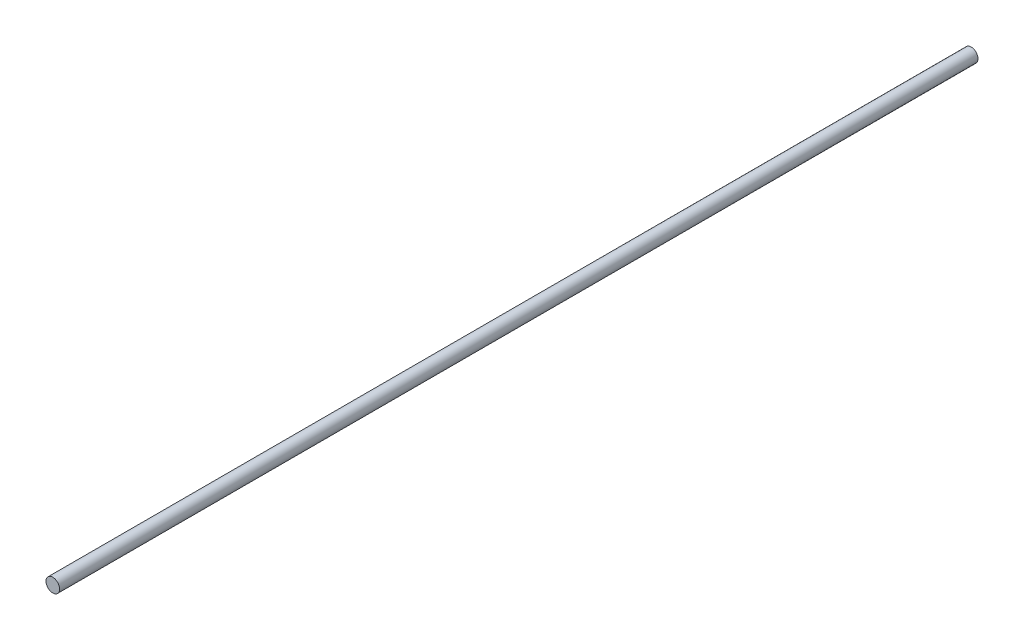
SolidWorks part; units mm, degrees
ref_plane "Front Plane" through (0, 0, 0) normal (0, 0, 1) x (1, 0, 0)
ref_plane "Top Plane" through (0, 0, 0) normal (0, 1, 0) x (1, 0, 0)
ref_plane "Right Plane" through (0, 0, 0) normal (1, 0, 0) x (0, 0, -1)
sketch "Sketch1" plane through (0, 0, 0) normal (0, 0, 1) x (1, 0, 0)
  circle A0 centre (0, 0) radius 4
  dimension "D1" = 8
extrude "Boss-Extrude1" add sketch "Sketch1" against normal blind 540
ref_plane "Plane2" through (0, 0, 1) normal (0, 0, 1) x (1, 0, 0)
sketch "Sketch2" plane through (0, 0, 1) normal (0, 0, 1) x (1, 0, 0)
  circle A1 centre (0, 0) radius 4.05
  dimension "D1" = 8.1
curve "Helix/Spiral1" pitch 8 height 540 turns 67.5
sketch "Sketch3" plane through (0, 0, 1) normal (0, 0, 1) x (1, 0, 0)
  circle A0 centre (0, 0) radius 4
  circle A1 centre (0, 0) radius 4
  circle A2 centre (0, 0) radius 4
  dimension "D1" = 0
sketch "Sketch4" plane through (0, 0, 1) normal (0, 0, 1) x (1, 0, 0)
  circle A0 centre (0, 0) radius 4 construction
  circle A1 centre (0, 0) radius 4
curve "Helix/Spiral2" pitch 8 height 540 turns 67.5
sketch "Sketch5" plane through (0, 0, 1) normal (0, 0, 1) x (1, 0, 0)
  circle A0 centre (0, 0) radius 4 construction
  circle A1 centre (0, 0) radius 4
curve "Helix/Spiral3" pitch 8 height 540 turns 67.5
sketch "Sketch6" plane through (0, 0, 1) normal (0, 0, 1) x (1, 0, 0)
  circle A0 centre (0, 0) radius 4 construction
  circle A1 centre (0, 0) radius 4
curve "Helix/Spiral4" pitch 8 height 540 turns 67.5
sketch "Sketch10" plane through (0, 0, 0) normal (0, 1, 0) x (1, 0, 0)
  line L0 (4.05, -1.67) -> (4.05, -0.33)
  line L1 (2.9, -1.3619) -> (2.9, -0.6519)
  line L2 (2.9, -1.3619) -> (4.05, -1.67)
  line L7 (2.9, -0.6519) -> (4.05, -0.33)
  point P4 (4.05, -1)
  dimension "D6" = 0.71
  dimension "D9" = 1.34
  dimension "D10" = 75
  dimension "D11" = 1.15
sweep "Cut-Sweep3" [suppressed] cut profiles "Sketch10" path "Helix/Spiral1"
sketch "Sketch11" plane through (0, 0, 0) normal (1, 0, 0) x (0, 0, -1)
  line L0 (2.33, -4) -> (3.67, -4)
  line L5 (3, -4) -> (2.9931, -2.85) construction
  line L6 (2.33, -4) -> (2.6381, -2.85)
  line L7 (3.67, -4) -> (3.3481, -2.85)
  line L8 (2.6381, -2.85) -> (3.3481, -2.85)
  dimension "D1" = 1.34
sweep "Cut-Sweep4" [suppressed] cut profiles "Sketch11" path "Helix/Spiral2"
sketch "Sketch12" plane through (0, 0, 1) normal (0, 0, 1) x (1, 0, 0)
  line L0 (-4, 0) -> (4, 0) construction
  circle A0 centre (0, 0) radius 4 construction
ref_plane "Plane3" through (0, 0, 0) normal (0, -1, 0) x (-1, 0, 0)
sketch "Sketch13" plane through (0, 0, 0) normal (0, -1, 0) x (-1, 0, 0)
  line L0 (4, -0.33) -> (4, -1.67)
  line L1 (2.85, -0.6419) -> (2.85, -1.3619)
  line L2 (2.85, -1.3619) -> (4, -1.67)
  line L3 (4, -0.33) -> (2.85, -0.6419)
  point P2 (4, -1)
  dimension "D1" = 1.34
  dimension "D2" = 0.72
  dimension "D3" = 1.15
  dimension "D4" = 75
sweep "Cut-Sweep5" [suppressed] cut profiles "Sketch13" path "Helix/Spiral3"
sketch "Sketch14" plane through (0, 0, 0) normal (1, 0, 0) x (0, 0, -1)
  line L0 (-1.67, -4) -> (-0.33, -4)
  line L1 (-1.3619, -2.85) -> (-0.6519, -2.85)
  line L2 (-0.6519, -2.85) -> (-0.33, -4)
  line L3 (-1.67, -4) -> (-1.3619, -2.85)
  point P4 (-1, -4)
  dimension "D1" = 1.34
  dimension "D2" = 0.71
  dimension "D3" = 1.15
  dimension "D4" = 75
sweep "Cut-Sweep6" [suppressed] cut profiles "Sketch14" path "Helix/Spiral4"
equation "\"D3@Helix/Spiral1\" = \"D1@Boss-Extrude1\""
equation "\"D3@Helix/Spiral2\"= \"D1@Boss-Extrude1\""
equation "\"D3@Helix/Spiral3\" = \"D1@Boss-Extrude1\""
equation "\"D3@Helix/Spiral4\"= \"D1@Boss-Extrude1\""
